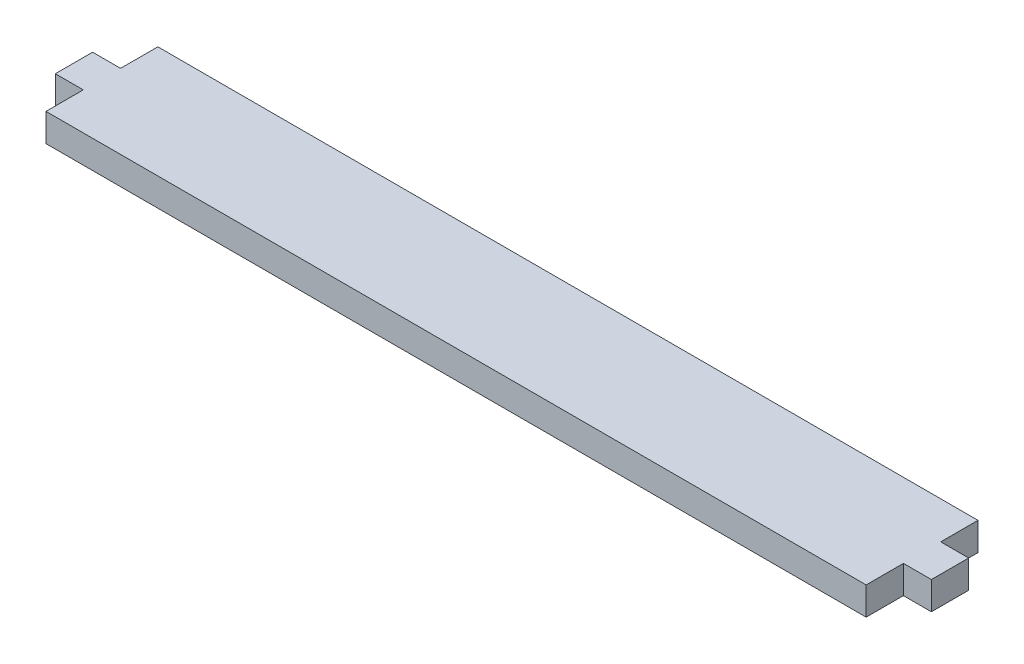
SolidWorks part; units mm, degrees
ref_plane "Front Plane" through (0, 0, 0) normal (0, 0, 1) x (1, 0, 0)
ref_plane "Top Plane" through (0, 0, 0) normal (0, 1, 0) x (1, 0, 0)
ref_plane "Right Plane" through (0, 0, 0) normal (1, 0, 0) x (0, 0, -1)
sketch "Sketch1" plane through (0, 0, 0) normal (0, 1, 0) x (1, 0, 0)
  line L1 (139.7, -19.05) -> (-139.7, -19.05)
  line L2 (139.7, -19.05) -> (139.7, 19.05)
  line L3 (139.7, 19.05) -> (-139.7, 19.05)
  line L4 (-139.7, -19.05) -> (-139.7, 19.05)
  line L5 (139.7, -19.05) -> (-139.7, 19.05) construction
  line L6 (139.7, 19.05) -> (-139.7, -19.05) construction
  point P0 (0, 0)
  dimension "D1" = 279.4
  dimension "D2" = 38.1
extrude "Boss-Extrude1" add sketch "Sketch1" along normal blind 9.525
sketch "Sketch2" plane through (139.7, 0, 0) normal (1, 0, 0) x (0, 0, -1)
  line L0 (-19.05, 0) -> (19.05, 0) construction
  line L1 (-6.35, 0) -> (6.35, 0)
  line L2 (-6.35, 0) -> (-6.35, 9.525)
  line L3 (-6.35, 9.525) -> (6.35, 9.525)
  line L4 (6.35, 0) -> (6.35, 9.525)
  line L5 (-19.05, 9.525) -> (19.05, 9.525) construction
  line L6 (-19.05, 9.525) -> (-19.05, 0) construction
  dimension "D1" = 12.7
  dimension "D2" = 12.7
extrude "Boss-Extrude2" add sketch "Sketch2" along normal blind 9.525
mirror "Mirror1" about plane through (0, 0, 0) normal (1, 0, 0) of "Boss-Extrude2"
sketch "Sketch3" plane through (0, 0, 0) normal (0, -1, 0) x (1, 0, 0)
  line L0 (-138.2612, -11.4174) -> (137.3788, -11.4174)
